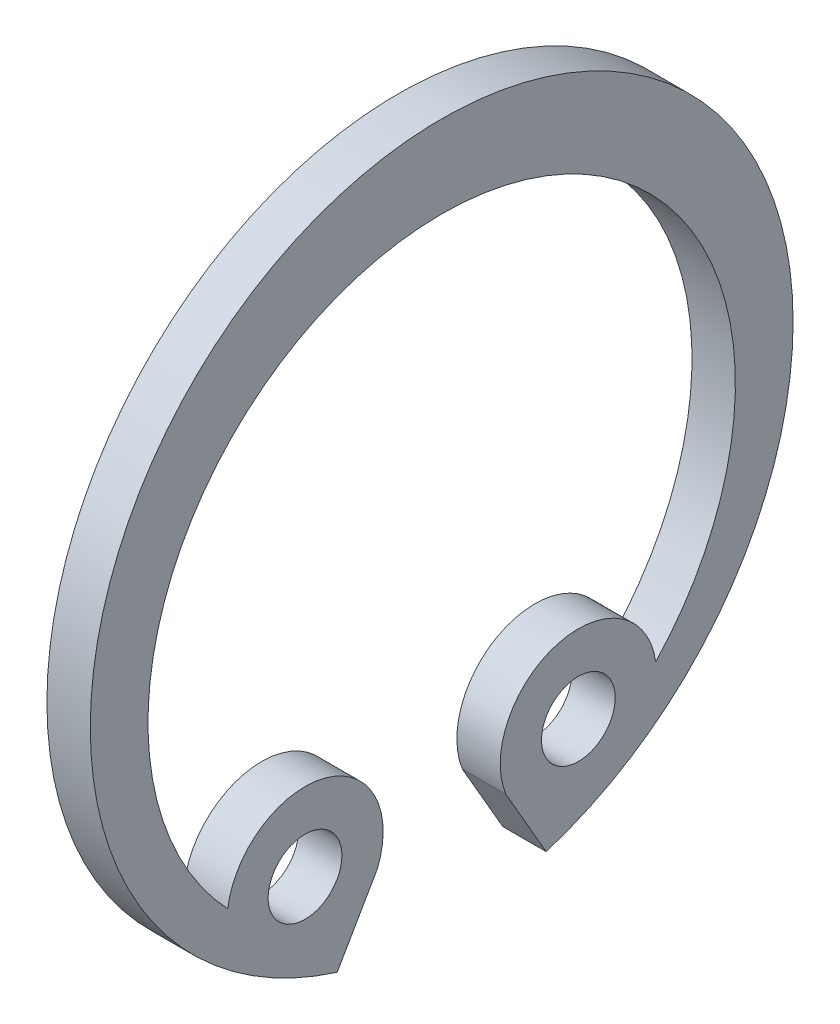
SolidWorks part; units mm, degrees
ref_plane "Front Plane" through (0, 0, 0) normal (0, 0, 1) x (1, 0, 0)
ref_plane "Top Plane" through (0, 0, 0) normal (0, 1, 0) x (1, 0, 0)
ref_plane "Right Plane" through (0, 0, 0) normal (1, 0, 0) x (0, 0, -1)
ref_plane "Plane1" through (0, 0, 0) normal (1, 0, 0) x (0, 0, -1)
sketch "Sketch1" plane through (0, 0, 0) normal (1, 0, 0) x (0, 0, -1)
  line L0 (-2.408, -7.7338) -> (-1.4786, -6.124)
  line L1 (1.4786, -6.124) -> (2.408, -7.7338)
  arc A0 (2.408, -7.7338) -> (-2.408, -7.7338) centre (0, 0) ccw
  arc A1 (-1.4786, -6.124) -> (-4.9327, -5.207) centre (-3.15, -5.456) ccw
  arc A2 (-4.9327, -5.207) -> (4.9327, -5.207) centre (0, -0.57) cw
  arc A3 (4.9327, -5.207) -> (1.4786, -6.124) centre (3.15, -5.456) ccw
  circle A4 centre (3.15, -5.456) radius 0.85
  circle A5 centre (-3.15, -5.456) radius 0.85
extrude "Boss-Extrude1" add sketch "Sketch1" against normal blind 0.5 and the other way blind 0.5
